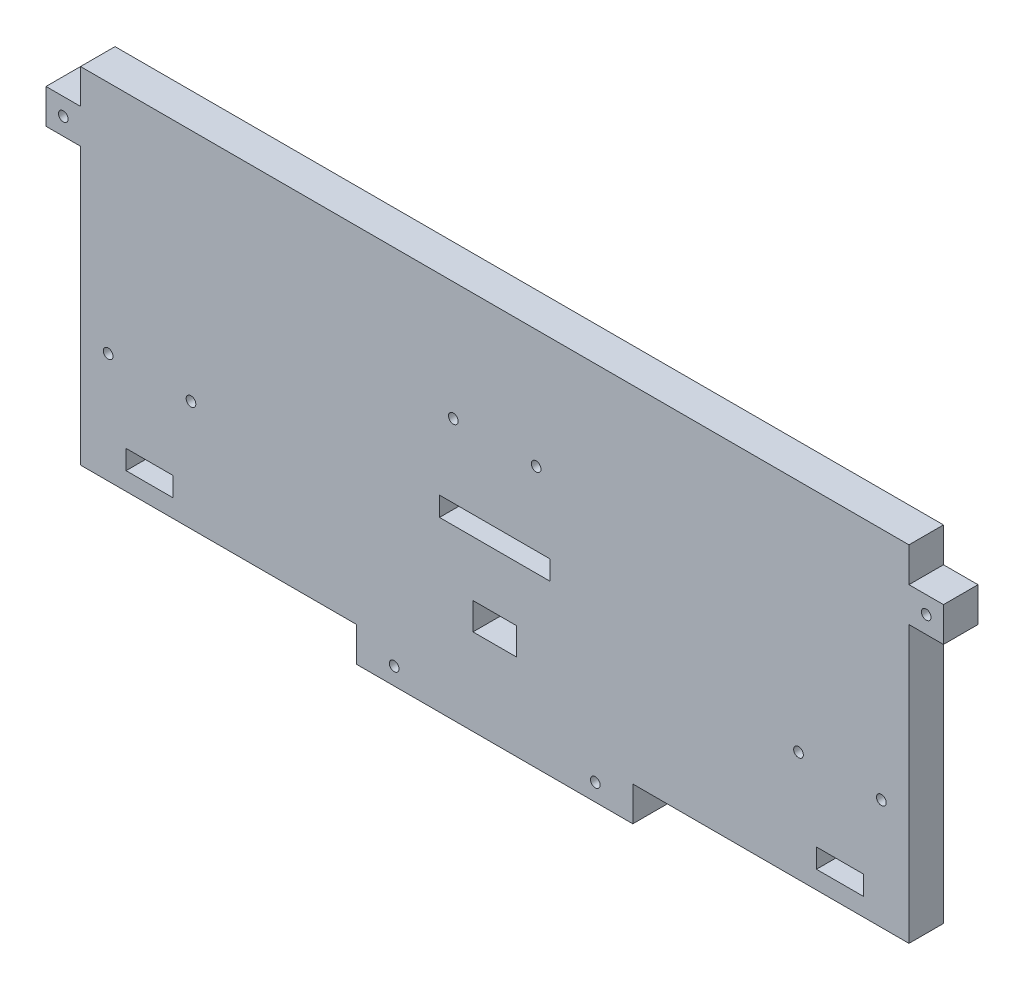
SolidWorks part; units mm, degrees
ref_plane "Front Plane" through (0, 0, 0) normal (0, 0, 1) x (1, 0, 0)
ref_plane "Top Plane" through (0, 0, 0) normal (0, 1, 0) x (1, 0, 0)
ref_plane "Right Plane" through (0, 0, 0) normal (1, 0, 0) x (0, 0, -1)
sketch "Sketch1" plane through (0, 0, 0) normal (0, 0, 1) x (1, 0, 0)
  line L0 (-4.0051, -10.0637) -> (-4.0051, 0.0963)
  line L1 (-80.2051, 38.9113) -> (-4.0051, 38.9113)
  line L2 (-80.2051, 38.9113) -> (-80.2051, 32.5613)
  line L3 (-80.2051, -24.5887) -> (-29.4051, -24.5887)
  line L4 (-4.0051, -10.0637) -> (-8.0051, -10.0637)
  line L5 (-80.2051, 32.5613) -> (-86.5551, 32.5613)
  line L6 (-4.0051, 3.6523) -> (-4.0051, 38.9113)
  line L7 (-80.2051, 26.2113) -> (-86.5551, 26.2113)
  line L8 (-86.5551, 32.5613) -> (-86.5551, 26.2113)
  line L9 (-4.0051, -15.0637) -> (-8.0051, -15.0637)
  line L10 (-8.0051, -10.0637) -> (-8.0051, -15.0637)
  line L11 (-63.1871, -17.7307) -> (-71.8231, -17.7307)
  line L12 (-80.2051, 26.2113) -> (-80.2051, -24.5887)
  line L13 (-4.0051, -30.9387) -> (-4.0051, -15.0637)
  line L14 (-29.4051, -24.5887) -> (-29.4051, -30.9387)
  line L15 (-29.4051, -30.9387) -> (-4.0051, -30.9387)
  line L16 (-63.1871, -17.7307) -> (-63.1871, -21.2867)
  line L17 (-63.1871, -21.2867) -> (-71.8231, -21.2867)
  line L18 (-71.8231, -17.7307) -> (-71.8231, -21.2867)
  line L19 (-4.0051, 0.0963) -> (-14.1651, 0.0963)
  line L21 (-4.0051, 3.6523) -> (-14.1651, 3.6523)
  line L22 (-14.1651, 0.0963) -> (-14.1651, 3.6523)
  circle A0 centre (-83.3801, 29.3863) radius 0.889
  circle A1 centre (-75.1251, -4.2687) radius 0.889
  circle A2 centre (-22.5051, -27.7637) radius 0.889
  circle A3 centre (-59.8851, -4.2687) radius 0.889
  circle A4 centre (-11.6251, 17.1143) radius 0.889
  dimension "D12" = 6.35
  dimension "D13" = 1.778
  dimension "D14" = 15.24
  dimension "D15" = 20.32
  dimension "D16" = 5.08
  dimension "D17" = 8.636
  dimension "D24" = 1.778
  dimension "D25" = 1.778
  dimension "D26" = 1.778
  dimension "D27" = 7.62
  dimension "D28" = 13.462
  dimension "D29" = 1.778
  dimension "D2" = 76.2
  dimension "D3" = 6.35
  dimension "D4" = 6.35
  dimension "D5" = 25.4
  dimension "D6" = 15.875
  dimension "D7" = 6.35
  dimension "D8" = 50.8
  dimension "D9" = 50.8
  dimension "D10" = 4
  dimension "D11" = 5
  dimension "D18" = 3.302
  dimension "D19" = 3.556
  dimension "D20" = 13.462
  dimension "D21" = 10.16
  dimension "D22" = 3.556
  dimension "D23" = 10.16
extrude "Boss-Extrude1" add sketch "Sketch1" along normal blind 6.35
mirror "Mirror1" about plane through (-4.0051, -10.0637, 6.35) normal (-1, 0, 0) of "Boss-Extrude1"
